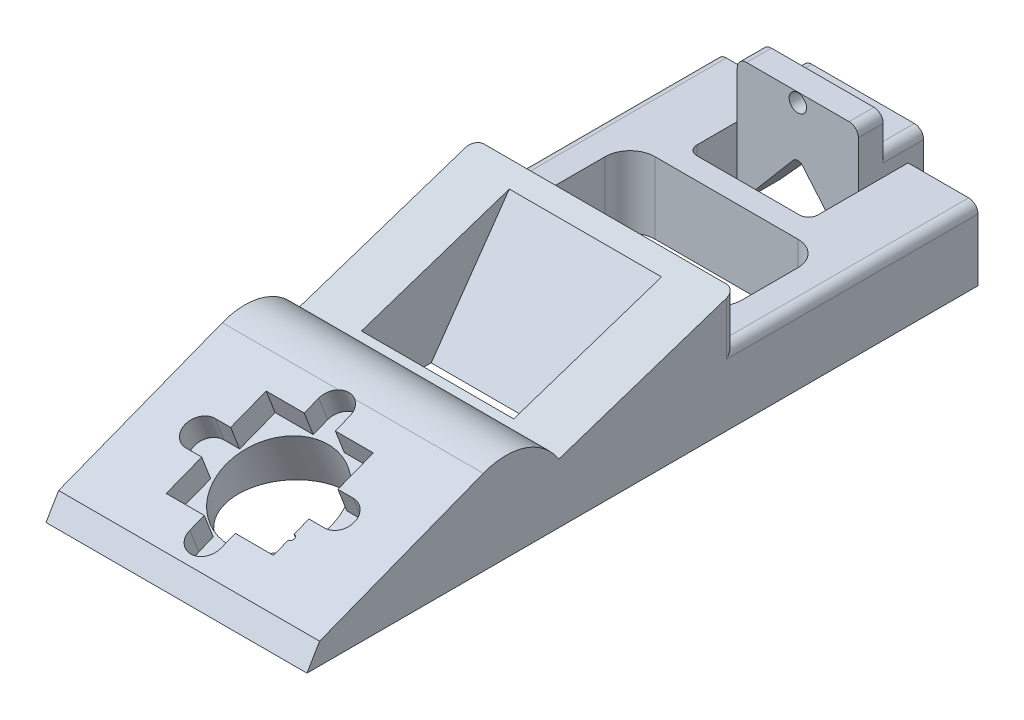
SolidWorks part; units mm, degrees
ref_plane "前视基准面" through (0, 0, 0) normal (0, 0, 1) x (1, 0, 0)
ref_plane "上视基准面" through (0, 0, 0) normal (0, 1, 0) x (1, 0, 0)
ref_plane "右视基准面" through (0, 0, 0) normal (1, 0, 0) x (0, 0, -1)
sketch "草图1" plane through (0, 0, 0) normal (0, 1, 0) x (1, 0, 0)
  line L1 (-21, 36.5) -> (21, 36.5)
  line L2 (-21, 36.5) -> (-21, -36.5)
  line L3 (-21, -36.5) -> (21, -36.5)
  line L4 (21, 36.5) -> (21, -36.5)
  line L5 (-21, 36.5) -> (21, -36.5) construction
  line L6 (-21, -36.5) -> (21, 36.5) construction
  point P0 (0, 0)
  dimension "D1" = 73
  dimension "D2" = 42
extrude "凸台-拉伸1" add sketch "草图1" along normal blind 19
sketch "草图3" plane through (-21, 0, 0) normal (-1, 0, 0) x (0, 0, 1)
  line L0 (-36.5, 11.5) -> (2.5, 11.5)
  line L1 (-36.5, 19) -> (-36.5, 0) construction
  line L2 (-36.5, 0) -> (36.5, 0) construction
  line L3 (2.5, 11.5) -> (2.5, 19)
  line L4 (-36.5, 19) -> (36.5, 19) construction
  line L5 (2.5, 19) -> (30.9777, 9.5649)
  line L6 (30.9777, 9.5649) -> (36.5, 0)
  line L7 (-36.5, 11.5) -> (-36.5, 19)
  line L8 (-36.5, 19) -> (2.5, 19)
  line L9 (36.5, 19) -> (36.5, 0)
  line M5 (36.5, 0) -> (36.5, 19)
  line M6 (36.5, 19) -> (-36.5, 19)
  line M7 (-36.5, 19) -> (-36.5, 0)
  dimension "D1" = 11.5
  dimension "D2" = 39
  dimension "D3" = 60
  dimension "D4" = 30
extrude "切除-拉伸1" cut sketch "草图3" against normal up to next contours L0 L3 M6 M7 | L5 L6 M5 M6 region at (-21, 15.25, -17) region at (-21, 14.294, 26.1192)
sketch "草图4" plane through (0, 11.5, 0) normal (0, 1, 0) x (1, 0, 0)
  line L0 (21, 36.5) -> (-21, 36.5) construction
  line L2 (-9.75, 28.5) -> (9.75, 28.5)
  line L3 (9.75, 28.5) -> (9.75, 22)
  line L4 (8.25, 20.5) -> (-8.25, 20.5)
  line L5 (-9.75, 22) -> (-9.75, 28.5)
  line L6 (21, -2.5) -> (21, 36.5) construction
  line L7 (-21, 36.5) -> (-21, -2.5) construction
  arc A0 (9.75, 22) -> (8.25, 20.5) centre (8.25, 22) cw
  arc A1 (-8.25, 20.5) -> (-9.75, 22) centre (-8.25, 22) cw
  point P5 (-0.2557, 36.5)
  point P11 (9.75, 20.5)
  dimension "D4" = 1.5
  dimension "D1" = 8
  dimension "D3" = 8
  dimension "D5" = 11.25
  dimension "D6" = 19.5
  dimension "D7" = 11.25
  dimension "D8" = 42
extrude "切除-拉伸2" cut sketch "草图4" against normal blind 19 contours A1 L4 A0 L3 L2 L5 region at (0, 11.5, -24.5228)
sketch "草图5" plane through (0, 11.5, 0) normal (0, 1, 0) x (1, 0, 0)
  line L0 (9.75, 28.5) -> (9.75, 32.5)
  line L1 (9.75, 32.5) -> (-9.75, 32.5)
  line L2 (-9.75, 32.5) -> (-9.75, 28.5)
  line L7 (-9.75, 28.5) -> (-9.75, 22)
  line L8 (9.75, 28.5) -> (-9.75, 28.5)
  line L9 (9.75, 22) -> (9.75, 28.5)
  line L10 (-8.25, 20.5) -> (8.25, 20.5)
  line L12 (9.75, 28.5) -> (-9.75, 28.5)
  arc A2 (-9.75, 22) -> (-8.25, 20.5) centre (-8.25, 22) ccw
  arc A3 (8.25, 20.5) -> (9.75, 22) centre (8.25, 22) ccw
  dimension "D1" = 4
  dimension "D2" = 0
extrude "凸台-拉伸2" add sketch "草图5" along normal blind 9
sketch "草图6" plane through (0, 11.5, 0) normal (0, 1, 0) x (1, 0, 0)
  line L0 (-9.75, 32.5) -> (-9.75, 39)
  line L1 (-9.75, 39) -> (9.75, 39)
  line L2 (9.75, 39) -> (9.75, 32.5)
  line L3 (9.75, 32.5) -> (-9.75, 32.5)
  dimension "D1" = 6.5
extrude "凸台-拉伸3" add sketch "草图6" against normal up to surface (11.5 mm away) and the other way blind 3.5 up to face at (0, 0, 0)
sketch "草图7" plane through (0, 0, -39) normal (0, 0, -1) x (-1, 0, 0)
  line L0 (-21, 11.5) -> (21, 11.5) construction
  line L1 (-21, 11.5) -> (21, 11.5)
  line L2 (0, 11.5) -> (-9.75, 0)
  line L3 (0, 11.5) -> (9.75, 0)
  line L4 (9.75, 0) -> (-9.75, 0)
  line M2 (-9.75, 0) -> (9.75, 0)
extrude "切除-拉伸3" cut sketch "草图7" against normal up to next contours L3 L2 M2 region at (0, 3.8333, -39)
fillet "圆角1" radius 1.5 4 edges at (-9.75, 15, -35.75) (9.75, 15, -35.75) (-9.75, 20.5, -30.5) (9.75, 20.5, -30.5)
fillet "圆角2" radius 1 1 edges at (0, 11.5, -33.75)
sketch "草图8" plane through (9.75, 0, 0) normal (1, 0, 0) x (0, 0, -1)
  line L0 (36.5, 0) -> (39, 4)
  line L1 (39, 13.5) -> (39, 0) construction
  line L2 (39, 4) -> (39, 0)
  line L3 (39, 0) -> (36.5, 0)
  dimension "D1" = 4
extrude "切除-拉伸4" cut sketch "草图8" against normal blind 20
fillet "圆角3" radius 1.5 2 edges at (-8.0543, 2, -37.75) (8.0543, 2, -37.75)
sketch "草图9" plane through (0, 17.867, 5.9196) normal (0, 0.9493, 0.3145) x (1, 0, 0)
  line L1 (-18, 3.6024) -> (18, 3.6024)
  line L2 (-18, 3.6024) -> (-18, -24.8476)
  line L3 (-18, -24.8476) -> (18, -24.8476)
  line L4 (21, -26.3976) -> (21, 3.6024)
  line L5 (21, 3.6024) -> (-21, 3.6024)
  line L6 (-21, 3.6024) -> (-21, -26.3976)
  line L7 (-21, -26.3976) -> (21, -26.3976)
  line L8 (21, -26.3976) -> (21, 3.6024)
  line L9 (21, 3.6024) -> (-21, 3.6024)
  line L10 (-21, 3.6024) -> (-21, -26.3976)
  line L11 (-21, -26.3976) -> (21, -26.3976)
  line L12 (18, 3.6024) -> (18, -24.8476)
  line L13 (-18, 3.6024) -> (18, -24.8476) construction
  line L14 (-18, -24.8476) -> (18, 3.6024) construction
  point P2 (0, -10.6226)
  dimension "D2" = 3
  dimension "D3" = 0
  dimension "D4" = 3
  dimension "D5" = 1.55
  dimension "D1" = 0
sketch "草图13" plane through (0, 14.07, 4.6616) normal (0, 0.9493, 0.3145) x (1, 0, 0)
  line L0 (9.0005, -12.7026) -> (10.0709, -12.7026) construction
  line L1 (-8.2495, -4.0776) -> (9.0005, -4.0776)
  line L2 (-8.2495, -4.0776) -> (-8.2495, -21.3276)
  line L3 (-8.2495, -21.3276) -> (9.0005, -21.3276)
  line L4 (9.0005, -4.0776) -> (9.0005, -21.3276)
  line L5 (-8.2495, -4.0776) -> (9.0005, -21.3276) construction
  line L6 (-8.2495, -21.3276) -> (9.0005, -4.0776) construction
  line L7 (10.0709, -12.7276) -> (10.0709, -12.6776)
  line L8 (9.0709, -13.7276) -> (8.8135, -13.7276)
  line L9 (9.0709, -11.6776) -> (8.8135, -11.6776)
  line L10 (0.3755, -21.3276) -> (0.3755, -23.9461) construction
  line L11 (-2.1245, -23.9461) -> (2.8755, -23.9461) construction
  line L12 (-2.1245, -23.9461) -> (-2.1245, -20.9461)
  line L13 (2.8755, -23.9461) -> (2.8755, -20.9461)
  line L14 (-999.6245, -12.7026) -> (49000.3755, -12.7026) construction
  line L15 (2.8755, -1.459) -> (2.8755, -4.459)
  line L16 (-2.1245, -1.459) -> (-2.1245, -4.459)
  arc A2 (10.0709, -12.7276) -> (9.0709, -13.7276) centre (9.0709, -12.7276) cw
  arc A3 (10.0709, -12.6776) -> (9.0709, -11.6776) centre (9.0709, -12.6776) ccw
  circle A4 centre (0.3755, -23.9461) radius 2.5
  circle A5 centre (0.3755, -1.459) radius 2.5
  point P12 (10.0709, -12.7026)
  point P23 (0.3755, -23.9461)
  dimension "D2" = 1
  dimension "D1" = 17.25
  dimension "D3" = 17.25
  dimension "D4" = 3
  dimension "D5" = 5
sketch "草图16" plane through (0, 14.07, 4.6616) normal (0, 0.9493, 0.3145) x (1, 0, 0)
  line L0 (9.0709, -13.7276) -> (8.8135, -13.7276) construction
  line L1 (9.0709, -11.6776) -> (8.8135, -11.6776) construction
  line L2 (9.0709, -13.7276) -> (8.8135, -13.7276)
  line L3 (9.0709, -11.6776) -> (8.8135, -11.6776)
  line L4 (8.8135, -11.6776) -> (8.8135, -13.7276)
  line L5 (9.0709, -11.6776) -> (9.0709, -13.7276)
  line L6 (10.0709, -12.6776) -> (10.0709, -12.7276)
  arc A0 (9.0709, -13.7276) -> (10.0709, -12.7276) centre (9.0709, -12.7276) ccw construction
  arc A1 (10.0709, -12.6776) -> (9.0709, -11.6776) centre (9.0709, -12.6776) ccw construction
  arc A2 (9.0709, -13.7276) -> (10.0709, -12.7276) centre (9.0709, -12.7276) ccw
  arc A3 (10.0709, -12.6776) -> (9.0709, -11.6776) centre (9.0709, -12.6776) ccw
sketch "草图17" plane through (0, 0, -28.5) normal (0, 0, -1) x (-1, 0, 0)
  line L0 (-9.75, 19) -> (9.75, 19)
  line L1 (-8.25, 20.5) -> (8.25, 20.5) construction
  circle A0 centre (0, 19) radius 1.4
  dimension "D1" = 2.8
  dimension "D2" = 1.5
extrude "切除-拉伸15" cut sketch "草图17" along normal blind 2 contours A0 L0 | A0 L0 region at (0, 19.5942, -28.5) region at (0, 18.4058, -28.5)
sketch "草图18" plane through (0, 0, -30.5) normal (0, 0, 1) x (1, 0, 0)
  circle A0 centre (0, 19) radius 0.75
  circle A1 centre (0, 19) radius 1.4 construction
  circle A2 centre (0, 19) radius 1.4
  dimension "D2" = 1.5
  dimension "D1" = 0
extrude "切除-拉伸16" cut sketch "草图18" against normal blind 4 contours A0 region at (0, 19, -30.5)
sketch "草图20" plane through (0, 0, -36.5) normal (0, 0, -1) x (-1, 0, 0)
  line L0 (-21, 11.5) -> (-9.75, 11.5) construction
  line L1 (-21, 11.5) -> (-21, 0) construction
  circle A0 centre (-15.25, 5.75) radius 0.75
  dimension "D3" = 1.5
  dimension "D1" = 5.75
  dimension "D2" = 5.75
extrude "切除-拉伸18" cut sketch "草图20" against normal blind 4 draft 5
mirror "镜向1" about plane through (0, 0, 0) normal (1, 0, 0) of "切除-拉伸18"
fillet "圆角7" radius 1.5 4 edges at (21, 11.5, -17) (-21, 11.5, -17) (21, 15.25, 2.5) (-21, 15.25, 2.5)
sketch "草图21" plane through (0, 0, 0) normal (0, -1, 0) x (1, 0, 0)
  line L0 (21, 30.9777) -> (-21, 30.9777) construction
  line L2 (21, 36.5) -> (21, -36.5) construction
  line L3 (-12.25, 5.6832) -> (12.25, 5.6832)
  line L6 (19.5, 2.5) -> (-19.5, 2.5) construction
  line L7 (19.5, 2.5) -> (-19.5, 2.5)
  line L11 (-21, -36.5) -> (-21, 36.5) construction
  line L13 (-12.25, 3.7294) -> (12.25, 3.7294)
  line L14 (-12.25, 3.7294) -> (-12.25, 29.4777)
  line L15 (-12.25, 29.4777) -> (12.25, 29.4777)
  line L16 (12.25, 3.7294) -> (12.25, 29.4777)
  point P10 (0, 5.6832)
  point P16 (0, 5.6832)
  dimension "D1" = 24.5
  dimension "D2" = 8.75
  dimension "D3" = 8.75
  dimension "D4" = 1.5
extrude "切除-拉伸22" cut sketch "草图21" against normal blind 24 contours L3 L16 L15 L14 region at (0, 0, 17.5805)
sketch "草图23" plane through (21, 0, 0) normal (1, 0, 0) x (0, 0, -1)
  line L0 (-36.5, 0) -> (-30.9777, 9.5649) construction
  line L1 (-36.5, 0) -> (-30.9777, 9.5649)
  line L2 (-4, 10) -> (-4, 18.503) construction
  line L3 (-4, 10) -> (-4, 18.503)
  line L4 (-71.5, 0) -> (-36.5, 0)
  line L5 (-71.5, 0) -> (-69.4682, 3.4456)
  line L7 (-30.9777, 9.5649) -> (-30.9777, 18.3649)
  line L8 (-30.9777, 18.3649) -> (-69.4682, 3.4456)
  line M5 (-30.9777, 9.5649) -> (-36.5, 0)
  dimension "D1" = 35
  dimension "D2" = 4
  dimension "D3" = 8.503
  dimension "D4" = 8.8
extrude "凸台-拉伸4" add sketch "草图23" against normal up to surface (42 mm away) contours L7 L8 L5 L4 M5 region at (21, 6.4649, 46.9154) up to face at (-21, 8.0113, 0.4129)
sketch "草图24" plane through (0, 26.405, 10.2349) normal (0, 0.9324, 0.3614) x (1, 0, 0)
  line L0 (1.5, -59.6524) -> (1.5, -57.1524)
  line L1 (7.625, -57.1524) -> (-9.625, -57.1524)
  line L2 (7.625, -57.1524) -> (7.625, -39.9024)
  line L3 (7.625, -39.9024) -> (-9.625, -39.9024)
  line L4 (-21, -22.2465) -> (-21, -63.5274)
  line L5 (-21, -63.5274) -> (21, -63.5274)
  line L6 (21, -63.5274) -> (21, -22.2465)
  line L7 (21, -22.2465) -> (-21, -22.2465)
  line L9 (-21, -63.5274) -> (21, -63.5274)
  line L10 (21, -63.5274) -> (21, -22.2465)
  line L11 (21, -22.2465) -> (-21, -22.2465)
  line L12 (-9.625, -57.1524) -> (-9.625, -39.9024)
  line L13 (7.625, -57.1524) -> (-9.625, -39.9024) construction
  line L14 (7.625, -39.9024) -> (-9.625, -57.1524) construction
  line L15 (-3.5, -59.6524) -> (-3.5, -57.1524)
  line L16 (-1001, -48.5274) -> (48999, -48.5274) construction
  line L17 (-3.5, -37.4024) -> (-3.5, -39.9024)
  line L18 (1.5, -37.4024) -> (1.5, -39.9024)
  line L20 (-12.125, -51.0274) -> (-9.625, -51.0274)
  line L21 (-9.625, -57.1524) -> (-9.625, -39.9024)
  line L22 (-9.625, -57.1524) -> (7.625, -57.1524)
  line L23 (7.625, -57.1524) -> (7.625, -39.9024)
  line L25 (-9.625, -39.9024) -> (7.625, -39.9024)
  line L26 (-12.125, -46.0274) -> (-9.625, -46.0274)
  line L27 (10.125, -46.0274) -> (7.625, -46.0274)
  line L28 (10.125, -51.0274) -> (7.625, -51.0274)
  line L29 (-9.625, -57.1524) -> (7.625, -39.9024) construction
  line L30 (7.625, -57.1524) -> (-9.625, -39.9024) construction
  line L31 (-3.5, -37.4024) -> (-3.5, -39.9024)
  line L32 (-9.625, -39.9024) -> (7.625, -39.9024)
  line L33 (-9.625, -39.9024) -> (-9.625, -57.1524)
  line L34 (-9.625, -57.1524) -> (7.625, -57.1524)
  line L36 (7.625, -39.9024) -> (7.625, -57.1524)
  line L37 (1.5, -37.4024) -> (1.5, -39.9024)
  line L38 (1.5, -59.6524) -> (1.5, -57.1524)
  line L39 (-3.5, -59.6524) -> (-3.5, -57.1524)
  line L40 (-9.625, -39.9024) -> (7.625, -57.1524) construction
  line L41 (-9.625, -57.1524) -> (7.625, -39.9024) construction
  line L42 (10.125, -46.0274) -> (7.625, -46.0274)
  line L43 (7.625, -39.9024) -> (7.625, -57.1524)
  line L44 (7.625, -39.9024) -> (-9.625, -39.9024)
  line L45 (-9.625, -39.9024) -> (-9.625, -57.1524)
  line L47 (7.625, -57.1524) -> (-9.625, -57.1524)
  line L48 (10.125, -51.0274) -> (7.625, -51.0274)
  line L49 (-12.125, -51.0274) -> (-9.625, -51.0274)
  line L50 (-12.125, -46.0274) -> (-9.625, -46.0274)
  line L51 (7.625, -39.9024) -> (-9.625, -57.1524) construction
  line L52 (-9.625, -39.9024) -> (7.625, -57.1524) construction
  line L53 (14, -68.5274) -> (14, -26.5274) [skipped]
  line L54 (-16, -28.5274) -> (-16, -70.5274) [skipped]
  line L57 (19, -33.5274) -> (-23, -33.5274) [skipped]
  circle A0 centre (-1, -59.6524) radius 2.5
  circle A1 centre (-1, -37.4024) radius 2.5
  circle A2 centre (-12.125, -48.5274) radius 2.5
  circle A3 centre (10.125, -48.5274) radius 2.5
  circle A4 centre (-1, -37.4024) radius 2.5
  circle A5 centre (-1, -59.6524) radius 2.5
  circle A6 centre (10.125, -48.5274) radius 2.5
  circle A7 centre (-12.125, -48.5274) radius 2.5
  point P2 (-1, -48.5274)
  point P5 (-1, -48.5274)
  point P17 (-1, -48.5274)
  point P85 (-1, -48.5274)
  dimension "D5" = 5
  dimension "D2" = 17.25
  dimension "D3" = 17.25
  dimension "D6" = 15
  dimension "D1" = 0
  dimension "D7" = 4
extrude "切除-拉伸23" cut sketch "草图24" against normal blind 4 contours L12 L1 L47 L2 L23 L43 L3 L44 L21 L45 | A3 | L28 A3 L23 | L43 A3 L27 | A2 | A2 L20 L12 | A2 L45 L26 | A1 | L18 A1 L3 | L44 A1 L17 | A0 | A0 L0 L1 | A0 L47 L15 region at (0.9416, 5.5477, 64.0448) region at (-1, 4.846, 65.8552) region at (-1, 8.8667, 55.4821) region at (-2.9416, 5.5477, 64.0448) region at (8.1834, 8.165, 57.2925) region at (8.1834, 9.5684, 53.6718) region at (10.125, 8.8667, 55.4821) region at (-10.1834, 8.165, 57.2925) region at (-10.1834, 9.5684, 53.6718) region at (-12.125, 8.8667, 55.4821) region at (0.9416, 12.1857, 46.9195) region at (-2.9416, 12.1857, 46.9195) region at (-1, 12.8874, 45.1091)
sketch "草图25" plane through (0, 22.6754, 8.7892) normal (0, 0.9324, 0.3614) x (1, 0, 0)
  line L0 (7.625, -57.1524) -> (-9.625, -39.9024) construction
  circle A0 centre (-1, -48.5274) radius 8.5
  dimension "D1" = 17
extrude "切除-拉伸24" cut sketch "草图25" against normal through all
ref_plane "基准面1" through (7.625, 7.9632, 57.8132) normal (0, 0.3614, -0.9324) x (-1, 0, 0)
sketch "草图27" plane through (0, 26.405, 10.2349) normal (0, 0.9324, 0.3614) x (1, 0, 0)
  line L0 (7.625, -57.1524) -> (7.625, -51.0274) construction
  line L1 (7.625, -57.1524) -> (7.625, -51.0274)
  circle A0 centre (7.625, -54.0899) radius 0.5
  dimension "D1" = 1
extrude "切除-拉伸25" cut sketch "草图27" against normal through all contours L1 A0 | L1 A0 region at (7.4128, 6.8564, 60.6687) region at (7.8372, 6.8564, 60.6687)
sketch "草图28" plane through (-12.25, 0, 0) normal (1, 0, 0) x (0, 0, -1)
  line L0 (-5.6832, 17.9453) -> (-18.2487, 0)
  line L4 (-5.6832, 17.9453) -> (-29.4777, 10.0619)
  line L5 (-29.4777, 10.0619) -> (-29.4777, 0)
  line L6 (-29.4777, 0) -> (-5.6832, 0)
  line L7 (-5.6832, 0) -> (-5.6832, 17.9453)
  line L8 (-5.6832, 17.9453) -> (-29.4777, 10.0619)
  line L9 (-29.4777, 10.0619) -> (-29.4777, 0)
  line L10 (-29.4777, 0) -> (-5.6832, 0)
  line L11 (-5.6832, 0) -> (-5.6832, 17.9453)
  line M8 (-29.4777, 0) -> (-5.6832, 0)
  line M9 (-5.6832, 0) -> (-5.6832, 17.9453)
  dimension "D2" = 55
  dimension "D1" = 0
extrude "凸台-拉伸5" add sketch "草图28" along normal up to surface (24.5 mm away) contours L0 M9 M8 region at (-12.25, 5.9818, 9.8717) up to face at (12.25, 7.0018, 17.5805)
fillet "圆角8" radius 10 1 edges at (0, 18.3649, 30.9777)
sketch "草图30" plane through (0, 11.5, 0) normal (0, 1, 0) x (1, 0, 0)
  line L0 (19.5, -2.5) -> (19.5, 36.5) construction
  line L1 (11.5, 0) -> (-11.5, 0)
  line L2 (15.5, 4) -> (15.5, 13)
  line L3 (11.5, 17) -> (-11.5, 17)
  line L4 (-15.5, 4) -> (-15.5, 13)
  line L5 (-19.5, 36.5) -> (-19.5, -2.5) construction
  arc A0 (-11.5, 17) -> (-15.5, 13) centre (-11.5, 13) ccw
  arc A1 (15.5, 13) -> (11.5, 17) centre (11.5, 13) ccw
  arc A2 (11.5, 0) -> (15.5, 4) centre (11.5, 4) ccw
  arc A3 (-11.5, 0) -> (-15.5, 4) centre (-11.5, 4) cw
  dimension "D3" = 4
  dimension "D1" = 4
  dimension "D2" = 4
extrude "切除-拉伸26" cut sketch "草图30" against normal blind 36
